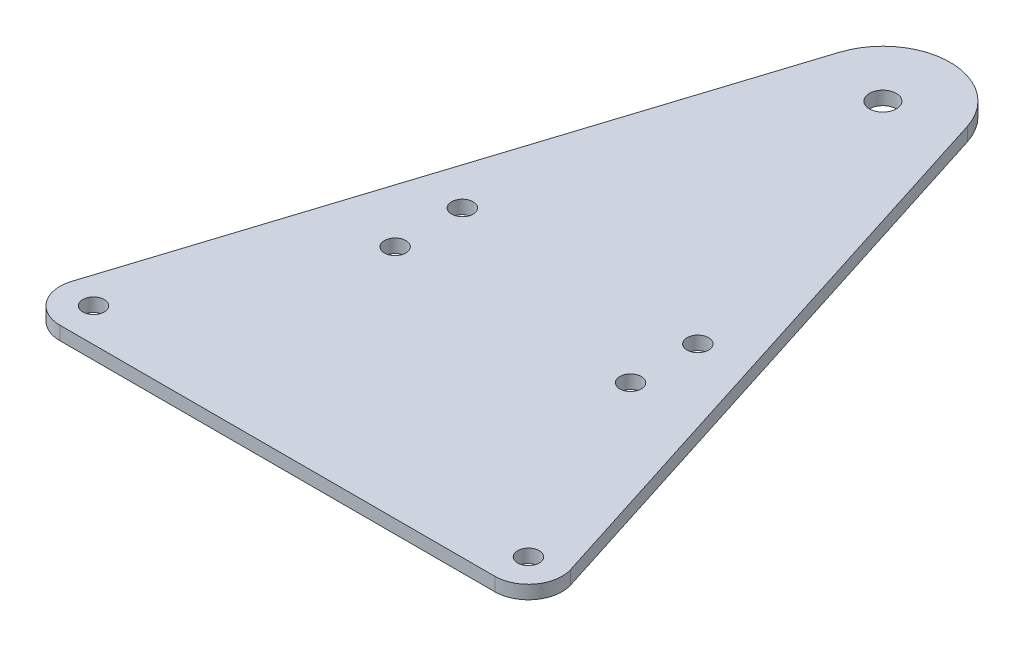
SolidWorks part; units mm, degrees
ref_plane "前视基准面" through (0, 0, 0) normal (0, 0, 1) x (1, 0, 0)
ref_plane "上视基准面" through (0, 0, 0) normal (0, 1, 0) x (1, 0, 0)
ref_plane "右视基准面" through (0, 0, 0) normal (1, 0, 0) x (0, 0, -1)
sketch "草图1" plane through (0, 0, 0) normal (0, 1, 0) x (1, 0, 0)
  line L1 (-75, -100) -> (75, -100)
  line L2 (-75, -100) -> (-75, 100)
  line L3 (-75, 100) -> (75, 100)
  line L4 (75, -100) -> (75, 100)
  line L5 (-75, -100) -> (75, 100) construction
  line L6 (-75, 100) -> (75, -100) construction
  point P0 (0, 0)
  dimension "D1" = 150
  dimension "D2" = 200
extrude "凸台-拉伸1" add sketch "草图1" along normal blind 2
sketch "草图2" plane through (0, 2, 0) normal (0, 1, 0) x (1, 0, 0)
  line L0 (0, 37.484) -> (0, -41.0202) construction
  circle A0 centre (0, 80) radius 2
  dimension "D1" = 4
  dimension "D2" = 80
extrude "切除-拉伸1" cut sketch "草图2" against normal up to next
sketch "草图3" plane through (0, 2, 0) normal (0, 1, 0) x (1, 0, 0)
  line L0 (0, 43.1419) -> (0, -43.9906) construction
  line L1 (-18.5355, 30) -> (18.9428, 30) construction
  circle A0 centre (-17.5, 35) radius 1.6
  circle A1 centre (-17.5, 25) radius 1.6
  circle A2 centre (17.5, 25) radius 1.6
  circle A3 centre (17.5, 35) radius 1.6
  circle A4 centre (0, 80) radius 2 construction
  dimension "D1" = 3.2
  dimension "D2" = 35
  dimension "D4" = 10
  dimension "D3" = 50
extrude "切除-拉伸2" cut sketch "草图3" against normal up to next
sketch "草图4" plane through (0, 2, 0) normal (0, 1, 0) x (1, 0, 0)
  line L1 (-43.8492, -5) -> (64.2178, -5) construction
  circle A0 centre (0, 80) radius 2 construction
  dimension "D1" = 85
sketch "草图5" plane through (0, 2, 0) normal (0, 1, 0) x (1, 0, 0)
  line L0 (-43.8492, -5) -> (64.2178, -5) construction
  line L1 (0, -2.5941) -> (0, -31.3254) construction
  circle A0 centre (32.3205, -5) radius 1.6
  circle A1 centre (-32.3205, -5) radius 1.6
  dimension "D1" = 3.2
  dimension "D2" = 32.3205
extrude "切除-拉伸3" cut sketch "草图5" against normal up to next
sketch "草图6" plane through (0, 2, 0) normal (0, 1, 0) x (1, 0, 0)
  line L0 (0, 107.0002) -> (0, -29.1005) construction
  line L1 (-17.5, 35) -> (-17.5, 25) construction
  line L2 (-17.5, 30) -> (17.5, 30) construction
  line L3 (17.5, 35) -> (17.5, 25) construction
  line L4 (-9.5284, 83.0348) -> (-37.0847, -3.4826)
  line L5 (9.5284, 83.0348) -> (37.0847, -3.4826)
  line L6 (-32.3205, -10) -> (32.3205, -10)
  circle A0 centre (-32.3205, -5) radius 5
  circle A1 centre (32.3205, -5) radius 5
  circle A2 centre (0, 80) radius 10
  circle M3 centre (32.3205, -5) radius 1.6
  circle M4 centre (-32.3205, -5) radius 1.6
  circle M5 centre (17.5, 35) radius 1.6
  circle M6 centre (17.5, 25) radius 1.6
  circle M7 centre (-17.5, 25) radius 1.6
  circle M8 centre (-17.5, 35) radius 1.6
  circle M9 centre (0, 80) radius 2
  dimension "D1" = 10
  dimension "D2" = 20
extrude "切除-拉伸4" cut sketch "草图6" against normal up to next (2 mm away) flip side to cut contours A2 L4 A0 L6 A1 L5 M5 M7 M8 M6 | A2 M9 | A1 M3 | A0 M4 region at (0, 2, -25.8151) region at (0, 2, -89.7172) region at (-31.5744, 2, 0.1991) region at (37.1215, 2, 4.2539)
